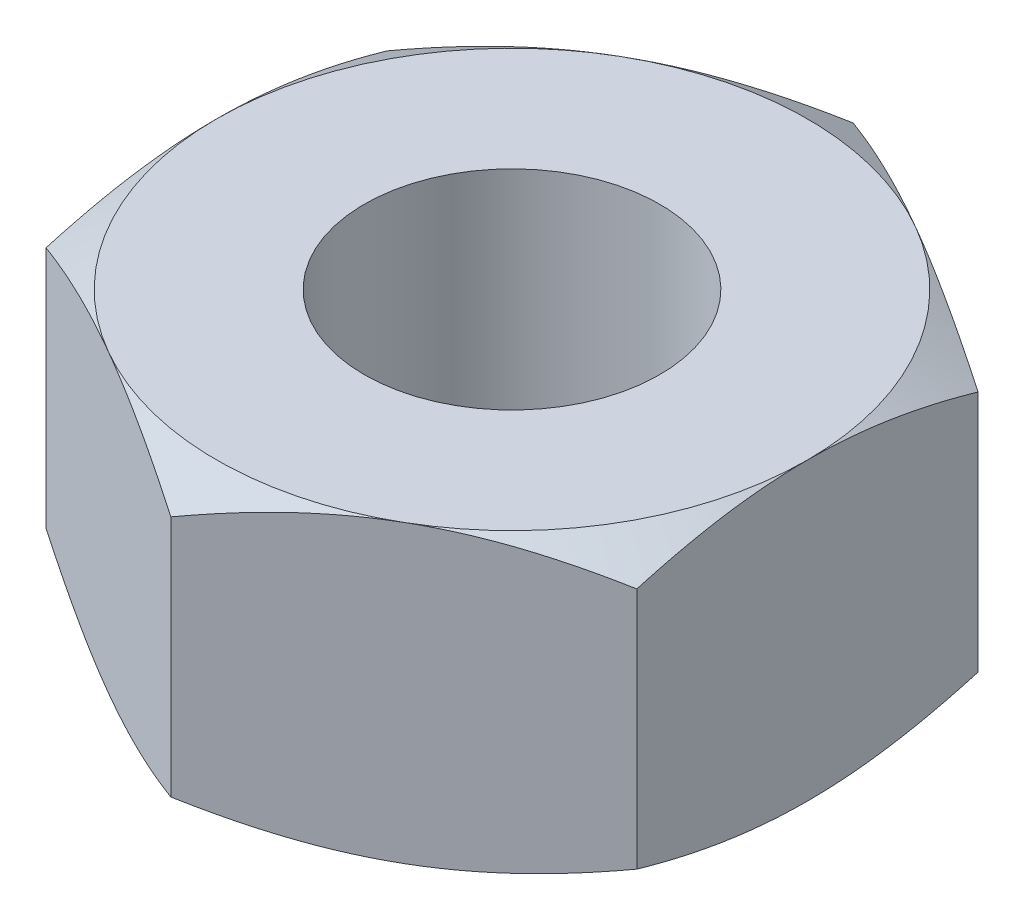
SolidWorks part; units mm, degrees
material "AISI 304"
ref_plane "Front Plane" through (0, 0, 0) normal (0, 0, 1) x (1, 0, 0)
ref_plane "Top Plane" through (0, 0, 0) normal (0, 1, 0) x (1, 0, 0)
ref_plane "Right Plane" through (0, 0, 0) normal (1, 0, 0) x (0, 0, -1)
sketch "Sketch1" plane through (0, 0, 0) normal (0, 1, 0) x (1, 0, 0)
  line L1 (-2, 1.1547) -> (-2, -1.1547)
  line L2 (-2, -1.1547) -> (0, -2.3094)
  line L3 (0, -2.3094) -> (2, -1.1547)
  line L4 (2, -1.1547) -> (2, 1.1547)
  line L5 (2, 1.1547) -> (0, 2.3094)
  line L6 (0, 2.3094) -> (-2, 1.1547)
  circle A0 centre (0, 0) radius 2 construction
  circle A1 centre (0, 0) radius 1
  dimension "Thread Size" = 2
  dimension "Hex" = 4
extrude "Boss-Extrude1" add sketch "Sketch1" along normal mid plane 2
sketch "Sketch2" plane through (0, 1, 0) normal (0, 1, 0) x (1, 0, 0)
  circle A0 centre (0, 0) radius 1 construction
  circle A1 centre (0, 0) radius 1
curve "Helix/Spiral1" [suppressed] pitch 0.4 height 2.4 turns 6 parameters "Pitch"=0.4
sketch "Sketch3" plane through (0, 0, 0) normal (1, 0, 0) x (0, 0, -1)
  line L0 (0.7402, 1.2) -> (1, 1.35)
  line L1 (1, 1.35) -> (1, 1)
  line L2 (1, 1) -> (0.7402, 1.15)
  line L3 (0.7402, 1.15) -> (0.7402, 1.2)
  line L4 (0.8701, 1.275) -> (0.8701, 1.075) construction
  line L5 (0.7402, 1.175) -> (1, 1.175) construction
  line L6 (1, 1) -> (-1, 1) construction
  dimension "D1" = 60
  dimension "D2" = 0.05
sweep "Sweep1" [suppressed] add profiles "Sketch3" path "Helix/Spiral1"
sketch "Sketch4" plane through (0, 1, 0) normal (0, 1, 0) x (1, 0, 0)
  circle A1 centre (0, 0) radius 1
  circle A2 centre (0, 0) radius 1
  dimension "D1" = 0
extrude "Cut-Extrude1" [suppressed] cut sketch "Sketch4" along normal through all and the other way through all draft 45
sketch "Sketch5" plane through (0, 1, 0) normal (0, 1, 0) x (1, 0, 0)
  circle A0 centre (0, 0) radius 2 construction
  circle A1 centre (0, 0) radius 2
extrude "Cut-Extrude2" cut sketch "Sketch5" against normal through all draft 60 flip side to cut
mirror "Mirror1" about plane through (0, 0, 0) normal (0, 1, 0) of "Cut-Extrude2", "Cut-Extrude1"
equation "\"D2@Sketch3\" = \"Pitch@Helix/Spiral1\"*.125"
equation "\"D3@Sketch3\" = \"Pitch@Helix/Spiral1\"*.5"
equation "\"D3@Helix/Spiral1\" = \"Height@Boss-Extrude1\"+\"Pitch@Helix/Spiral1\""
